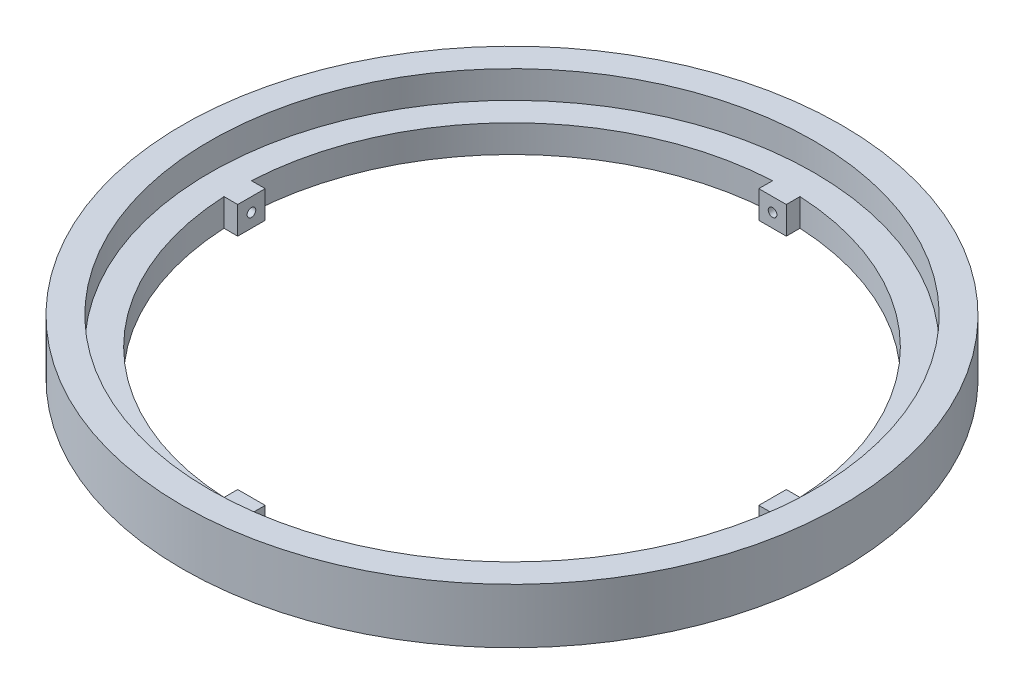
SolidWorks part; units mm, degrees
ref_plane "Front Plane" through (0, 0, 0) normal (0, 0, 1) x (1, 0, 0)
ref_plane "Top Plane" through (0, 0, 0) normal (0, 1, 0) x (1, 0, 0)
ref_plane "Right Plane" through (0, 0, 0) normal (1, 0, 0) x (0, 0, -1)
sketch "Sketch1" plane through (0, 0, 0) normal (0, 1, 0) x (1, 0, 0)
  circle A0 centre (0, 0) radius 139.7
  circle A1 centre (0, 0) radius 127
  circle A2 centre (0, 0) radius 152.4
extrude "Boss-Extrude1" add sketch "Sketch1" along normal blind 25.4 contours A2 A0 region at (-148.0895, 0, 0)
extrude "Boss-Extrude2" add sketch "Sketch1<3>" along normal blind 12.7 contours A0 A1 region at (-135.7487, 0, 0)
sketch "Sketch1<3>" plane through (0, 0, 0) normal (0, 1, 0) x (1, 0, 0) same geometry as "Sketch1"
sketch "Sketch2" plane through (0, 0, 0) normal (0, -1, 0) x (1, 0, 0)
  line L0 (0, -127) -> (0, -120.4912)
  line L1 (-6.35, -120.4912) -> (6.35, -120.4912)
  line L2 (6.35, -120.4912) -> (6.35, -123.6662)
  line L3 (6.35, -123.6662) -> (-6.35, -123.6662)
  line L4 (-6.35, -123.6662) -> (-6.35, -120.4912)
  line L5 (-6.35, -120.4912) -> (-6.35, -126.8412)
  line L6 (6.35, -120.4912) -> (6.35, -126.8412)
  line L7 (-120.4912, -6.35) -> (-126.8412, -6.35)
  line L8 (-120.4912, 6.35) -> (-126.8412, 6.35)
  line L9 (-120.4912, 6.35) -> (-120.4912, -6.35)
  line L10 (-6.35, 120.4912) -> (-6.35, 126.8412)
  line L11 (6.35, 120.4912) -> (6.35, 126.8412)
  line L12 (6.35, 120.4912) -> (-6.35, 120.4912)
  line L13 (120.4912, 6.35) -> (126.8412, 6.35)
  line L14 (120.4912, -6.35) -> (126.8412, -6.35)
  line L15 (120.4912, -6.35) -> (120.4912, 6.35)
  circle A0 centre (0, 0) radius 127 construction
  point P9 (0, -120.4912)
  point P28 (0, 0)
  circle M2 centre (0, 0) radius 127
  dimension "D1" = 3.175
  dimension "D2" = 3.175
  dimension "D4" = 12.7
  dimension "D3" = 4
extrude "Boss-Extrude3" add sketch "Sketch2" against normal blind 12.7 contours L9 L8 L7 M2 | L12 L11 L10 M2 | L15 L14 L13 M2 | L6 L3 L0 M2 | L3 L2 L1 L0 | L4 L3 L0 L1 | L3 L5 L0 M2 region at (-3.1494, 0, -125.3069) region at (3.1494, 0, -125.3069) region at (-3.175, 0, -122.0787) region at (3.175, 0, -122.0787) region at (-123.7193, 0, 0) region at (123.7193, 0, 0) region at (0, 0, 123.7193)
sketch "Sketch3" plane through (-120.4912, 0, 0) normal (1, 0, 0) x (0, 0, -1)
  line L0 (0, 12.7) -> (0, 0)
  line L1 (-6.35, 12.7) -> (6.35, 12.7) construction
  line L2 (-6.35, 0) -> (6.35, 0) construction
  circle A0 centre (0, 6.35) radius 2
extrude "Cut-Extrude1" cut sketch "Sketch3" against normal blind 25.4 contours L0 A0 | L0 A0 region at (-120.4912, 6.35, -0.8488) region at (-120.4912, 6.35, 0.8488)
pattern_circular "CirPattern1" count 4 every 90 about axis through (0, 12.7, 0) along (0, 1, 0) of "Cut-Extrude1"
